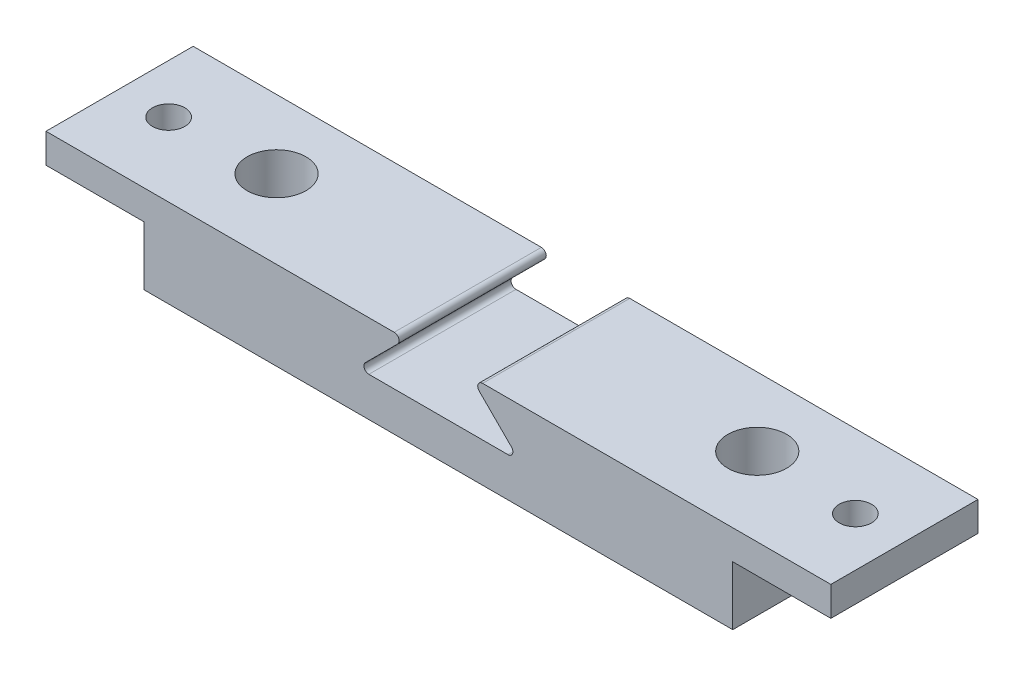
SolidWorks part; units mm, degrees
ref_plane "Спереди" through (0, 0, 0) normal (0, 0, 1) x (1, 0, 0)
ref_plane "Сверху" through (0, 0, 0) normal (0, 1, 0) x (1, 0, 0)
ref_plane "Справа" through (0, 0, 0) normal (1, 0, 0) x (0, 0, -1)
sketch "Эскиз1" plane through (0, 0, 0) normal (0, 1, 0) x (1, 0, 0)
  line L0 (-622.9617, 0) -> (30525.1229, 0) construction
  line L1 (-40, 7.5) -> (40, 7.5)
  line L2 (-40, 7.5) -> (-40, -7.5)
  line L3 (-40, -7.5) -> (40, -7.5)
  line L4 (40, 7.5) -> (40, -7.5)
  line L5 (0, -622.9617) -> (0, 30525.1229) construction
  line L6 (-24.5, 0.5) -> (24.5, 0.5) construction
  line L7 (-30, 7.5) -> (30, 7.5)
  line L8 (-30, 7.5) -> (-30, -7.5)
  line L9 (-30, -7.5) -> (30, -7.5)
  line L10 (30, 7.5) -> (30, -7.5)
  circle A0 centre (-35, 0) radius 1.65
  circle A1 centre (35, 0) radius 1.65
  circle A2 centre (-24.5, 0.5) radius 3
  circle A3 centre (24.5, 0.5) radius 3
  dimension "D2" = 3.3
  dimension "D8" = 6
  dimension "D1" = 70
  dimension "D3" = 80
  dimension "D4" = 15
  dimension "D5" = 60
  dimension "D6" = 49
  dimension "D7" = 0.5
extrude "Бобышка-Вытянуть1" add sketch "Эскиз1" along normal blind 6 contours L10 L7 L8 L9 A3 A2 region at (0, 0, 0.0335)
extrude "Бобышка-Вытянуть2" add sketch "Эскиз1<3>" along normal blind 3 from surface contours L4 L1 L2 L3 A1 A0 L7 L10 L9 L8 | L10 L7 L8 L9 A3 A2 | L1 L10 L3 L4 A1 region at (-35, 0, -7.3197) region at (0, 0, 0.0335) region at (35, 0, -7.3197) starting at face at (24.5, 6, 2.5)
sketch "Эскиз1<3>" plane through (0, 0, 0) normal (0, 1, 0) x (1, 0, 0) same geometry as "Эскиз1"
sketch "Эскиз2" plane through (0, 0, 0) normal (0, 0, 1) x (1, 0, 0)
  line L0 (4.1536, 8.1464) -> (7.4464, 4.8536)
  line L1 (40, 9) -> (-40, 9) construction
  line L2 (7.0929, 4) -> (-7.0929, 4)
  line L3 (-7.4464, 4.8536) -> (-4.1536, 8.1464)
  line L4 (0, -1000) -> (0, 49000) construction
  line L7 (-4.5071, 9) -> (4.5071, 9)
  arc A0 (-7.4464, 4.8536) -> (-7.0929, 4) centre (-7.0929, 4.5) ccw
  arc A1 (7.4464, 4.8536) -> (7.0929, 4) centre (7.0929, 4.5) cw
  arc A2 (4.5071, 9) -> (4.1536, 8.1464) centre (4.5071, 8.5) ccw
  arc A3 (-4.1536, 8.1464) -> (-4.5071, 9) centre (-4.5071, 8.5) ccw
  point P4 (0, 4)
  point P12 (-3.3, 9)
  point P16 (-8.3, 4)
  point P19 (8.3, 4)
  point P28 (3.3, 9)
  dimension "D3" = 0.5
  dimension "D2" = 6.6
  dimension "D1" = 16.6
  dimension "D5" = 5
extrude "Вырез-Вытянуть1" cut sketch "Эскиз2" against normal through all both and the other way through all
